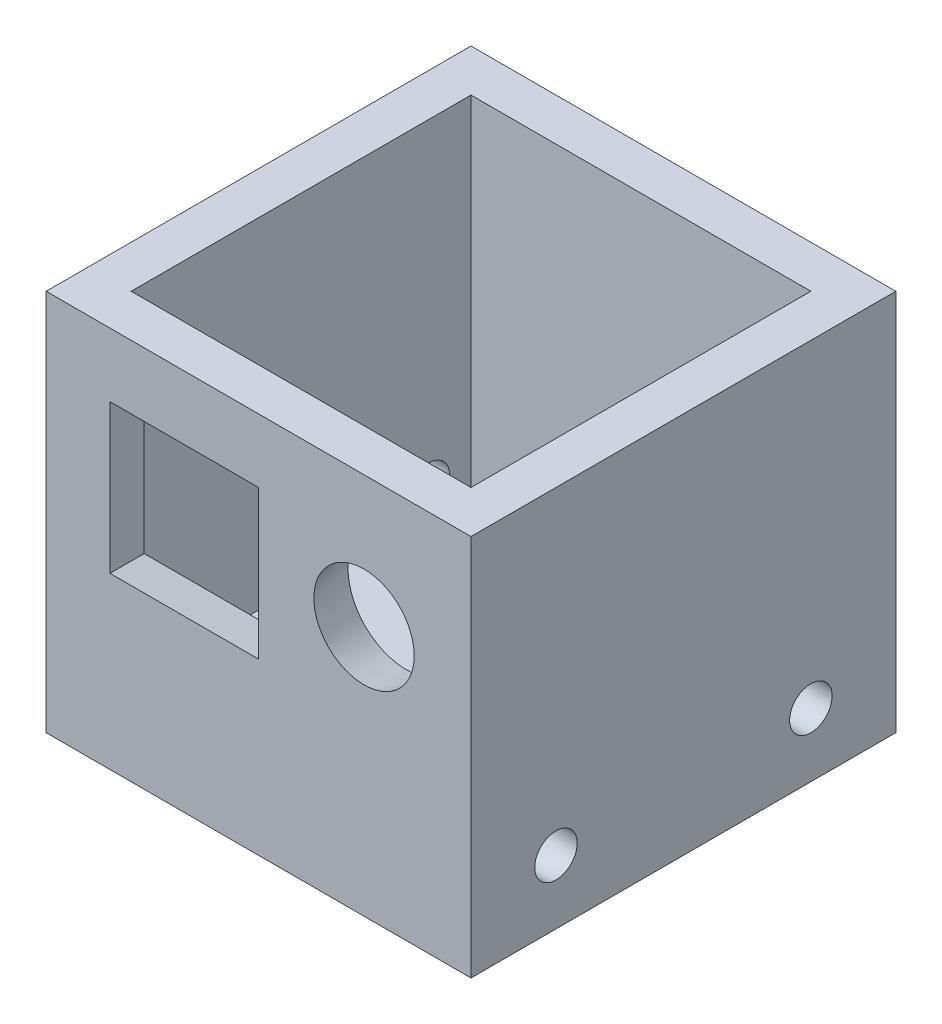
SolidWorks part; units mm, degrees
ref_plane "Plan de face" through (0, 0, 0) normal (0, 0, 1) x (1, 0, 0)
ref_plane "Plan de dessus" through (0, 0, 0) normal (0, 1, 0) x (1, 0, 0)
ref_plane "Plan de droite" through (0, 0, 0) normal (1, 0, 0) x (0, 0, -1)
sketch "Esquisse1" plane through (0, 0, 0) normal (0, 1, 0) x (1, 0, 0)
  line L1 (0, 0) -> (10, 0)
  line L2 (0, 0) -> (0, 10)
  line L3 (0, 10) -> (10, 10)
  line L4 (10, 0) -> (10, 10)
  point P5 (9, 1)
  point P9 (1, 1)
  point P16 (1, 9)
  point P19 (9, 9)
  dimension "D1" = 10
  dimension "D2" = 10
  dimension "D3" = 1
  dimension "D4" = 1
  dimension "D5" = 1
  dimension "D6" = 1
  dimension "D7" = 1
  dimension "D8" = 1
  dimension "D9" = 1
  dimension "D10" = 1
extrude "Boss.-Extru.1" add sketch "Esquisse1" along normal blind 9
sketch "Esquisse3" plane through (0, 0, 0) normal (0, 0, 1) x (1, 0, 0)
  line L0 (0, 9) -> (0, 0) construction
  line L1 (1.5, 7.5) -> (5, 7.5)
  line L2 (1.5, 7.5) -> (1.5, 4)
  line L3 (1.5, 4) -> (5, 4)
  line L4 (5, 7.5) -> (5, 4)
  line L10 (0, 0) -> (10, 0) construction
  line L12 (0, 9) -> (10, 9) construction
  circle A0 centre (7.4815, 5.8978) radius 1.1806
  point P4 (7.4815, 5.8978)
  dimension "D1" = 1.5
  dimension "D3" = 4
  dimension "D5" = 3.5
  dimension "D7" = 1.5
extrude "Enlèv. mat.-Extru.3" cut sketch "Esquisse3" against normal blind 1.25 draft 11 draft outward yes
sketch "Esquisse4" plane through (0, 0, -10) normal (0, 0, -1) x (-1, 0, 0)
  line L2 (0, 9) -> (0, 0) construction
  line L3 (-10, 4) -> (0, 4)
  ellipse E0 centre (-5, 4) end of major axis (0, 4) minor radius 3.576 (0, 4) -> (-10, 4) ccw
  point P7 (-5, 4)
sketch "Esquisse5" plane through (0, 9, 0) normal (0, 1, 0) x (1, 0, 0)
  line L0 (0, 0) -> (10, 0) construction
  line L1 (9, 9) -> (1, 9)
  line L2 (9, 9) -> (9, 1)
  line L3 (9, 1) -> (1, 1)
  line L4 (1, 9) -> (1, 1)
  line L5 (10, 10) -> (0, 10) construction
  line L6 (10, 0) -> (10, 10) construction
  line L7 (0, 10) -> (0, 0) construction
  dimension "D1" = 1
  dimension "D2" = 1
  dimension "D3" = 1
  dimension "D4" = 1
extrude "Enlèv. mat.-Extru.4" cut sketch "Esquisse5" against normal blind 8
sketch "Esquisse7" plane through (10, 0, 0) normal (1, 0, 0) x (0, 0, -1)
  line L0 (0, 9) -> (0, 0) construction
  line L1 (10, 9) -> (10, 0) construction
  line L2 (0, 0) -> (10, 0) construction
  circle A0 centre (2, 1.5) radius 0.5
  circle A1 centre (8, 1.5) radius 0.5
  dimension "D3" = 1.5
  dimension "D5" = 1
  dimension "D6" = 1
  dimension "D1" = 2
  dimension "D2" = 2
  dimension "D4" = 1.5
extrude "Enlèv. mat.-Extru.5" cut sketch "Esquisse7" against normal through all
